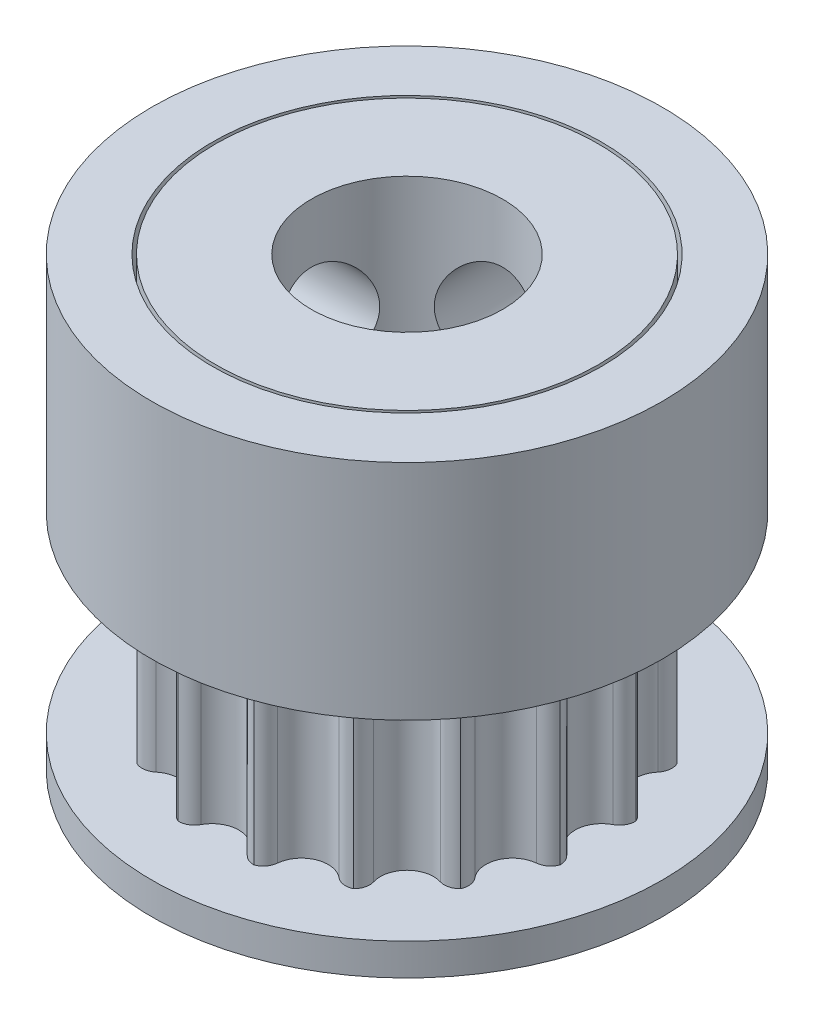
SolidWorks part; units mm, degrees
ref_plane "Front plan" through (0, 0, 0) normal (0, 0, 1) x (1, 0, 0)
ref_plane "Top plan" through (0, 0, 0) normal (0, 1, 0) x (1, 0, 0)
ref_plane "Right plan" through (0, 0, 0) normal (1, 0, 0) x (0, 0, -1)
sketch "Skica2" plane through (0, 0, 0) normal (0, 0, 1) x (1, 0, 0)
  line L0 (8, 7.5) -> (3, 7.5)
  line L1 (3, 7.5) -> (3, -7.5)
  line L2 (3, -7.5) -> (6.11, -7.5)
  line L3 (0, -7.5) -> (0, 7.5) construction
  line L4 (0, 7.5) -> (3, 7.5)
  line L5 (0, -7.5) -> (3, -7.5)
  line L6 (6.11, -7.5) -> (6.11, -6.5)
  line L7 (8, 0.5) -> (6.11, 0.5)
  line L8 (6.11, 0.5) -> (6.11, -5.5)
  line L9 (8, 0.5) -> (8, 7.5)
  line L12 (8, -6.5) -> (6.11, -6.5)
  line L14 (8, -6.5) -> (8, -5.5)
  line L15 (6.11, -5.5) -> (8, -5.5)
  point P6 (7.055, -6.5)
  point P7 (0, 0)
  dimension "D3" = 12.22
  dimension "D1" = 6
  dimension "D2" = 1
  dimension "D4" = 1
  dimension "D5" = 6
  dimension "D6" = 16
  dimension "D8" = 15
revolve "Revolute" add sketch "Skica2" angle 360 about L3 region at (5.1669, 0.6731, 0)
sketch "Sketch2" plane through (0, 0.5, 0) normal (0, -1, 0) x (1, 0, 0)
  line L0 (0, 0) -> (0, 6.11) construction
  line L1 (0, 0) -> (3, 5.3101) construction
  line L2 (0, 0) -> (1.6183, 5.8743) construction
  line L3 (0, 0) -> (-1.6183, 5.8743) construction
  circle A1 centre (0, 0) radius 5.274 construction
  circle A2 centre (0, 0) radius 5.61 construction
  arc A3 (-0.7387, 5.7185) -> (0.7387, 5.7185) centre (0, 6.11) ccw
  circle A4 centre (0, 0) radius 6.11 construction
  circle A5 centre (0, 0) radius 6.11 construction
  arc A7 (2.2516, 5.6827) -> (3.7026, 4.857) centre (3, 5.3101) ccw construction
  arc A8 (0, 7.3117) -> (1.6183, 5.8743) centre (0.4048, 6.1378) cw
  circle A9 centre (0, 0) radius 6.11 construction
  arc A10 (1.2857, 5.9732) -> (1.6218, 5.8908) centre (0, 0) cw
  arc A11 (1.2857, 5.9732) -> (0.7387, 5.7185) centre (1.1804, 5.4844) ccw
  arc A12 (0, 7.3117) -> (-1.6183, 5.8743) centre (-0.4048, 6.1378) ccw
  arc A13 (-1.2857, 5.9732) -> (-0.7387, 5.7185) centre (-1.1804, 5.4844) cw
  circle M8 centre (0, 0) radius 6.11
  dimension "D1" = 3
  dimension "D2" = 1
  dimension "D3" = 1.2417
  dimension "D4" = 0.836
  dimension "D5" = 6.11
extrude "Cut-Extrude1" cut sketch "Sketch2" along normal up to surface (6 mm away) contours A8 M8 | A11 A3 M8 region at (0, 0.5, 5.7583) region at (0, 0.5, 6.6333) up to face at (8, -5.5, 0)
pattern_circular "CirPattern1" count 16 over 360 about axis through (0, -7.5, 0) along (0, -1, 0) of "Cut-Extrude1" reverse direction yes
sketch "Sketch3" plane through (0, 0, 0) normal (1, 0, 0) x (0, 0, -1)
  line L0 (0, 7.5) -> (0, 0.5) construction
  line L1 (3, 7.5) -> (-3, 7.5) construction
  line L2 (-0.7387, 0.5) -> (0.7387, 0.5) construction
  circle A0 centre (0, 4) radius 1.65
  dimension "D1" = 3.3
extrude "Cut-Extrude2" cut sketch "Sketch3" against normal up to next
sketch "Sketch4" plane through (0, 0, 0) normal (0, 0, 1) x (1, 0, 0)
  line L0 (0, 7.5) -> (0, 0.5) construction
  line L1 (8, 7.5) -> (-8, 7.5) construction
  line L2 (-0.7387, 0.5) -> (0.7387, 0.5) construction
  circle A0 centre (0, 4) radius 1.65
  dimension "D1" = 3.3
extrude "Cut-Extrude3" cut sketch "Sketch4" against normal up to next
sketch "Sketch5" plane through (0, 7.5, 0) normal (0, 1, 0) x (1, 0, 0)
  circle A0 centre (0, 0) radius 6
  circle A1 centre (0, 0) radius 3 construction
  dimension "D1" = 3
extrude "Cut-Extrude-Thin1" cut sketch "Sketch5" against normal blind 5 thin thin type one direction wall 0.1
chamfer "Chamfer1" distance 1 angle 45 1 edges at (6.11, -6.5, 0)
equation "\"`\"=2"
